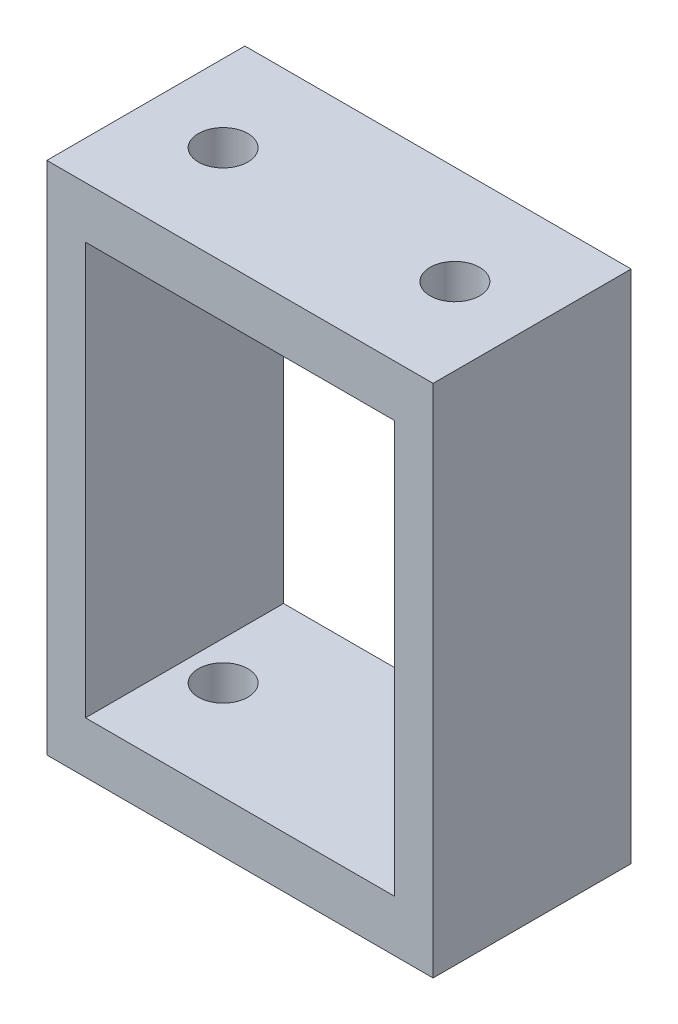
SolidWorks part; units mm, degrees
ref_plane "Front Plane" through (0, 0, 0) normal (0, 0, 1) x (1, 0, 0)
ref_plane "Top Plane" through (0, 0, 0) normal (0, 1, 0) x (1, 0, 0)
ref_plane "Right Plane" through (0, 0, 0) normal (1, 0, 0) x (0, 0, -1)
sketch "Sketch1" plane through (0, 0, 0) normal (0, 0, 1) x (1, 0, 0)
  line L1 (-9.75, -13) -> (9.75, -13)
  line L2 (-9.75, -13) -> (-9.75, 13)
  line L3 (-9.75, 13) -> (9.75, 13)
  line L4 (9.75, -13) -> (9.75, 13)
  line L5 (-9.75, -13) -> (9.75, 13) construction
  line L6 (-9.75, 13) -> (9.75, -13) construction
  line L11 (-6.533, -8.7106) -> (32.8535, 43.8047) construction
  line L12 (-23.2087, 23.2087) -> (23.2087, -23.2087) construction
  point P0 (0, 0)
  point P6 (0, 0)
  dimension "D1" = 19.5
  dimension "D2" = 26
extrude "Boss-Extrude1" add sketch "Sketch1" along normal blind 10
sketch "Sketch2" plane through (0, 0, 10) normal (0, 0, 1) x (1, 0, 0)
  line L1 (-7.8, -10.4) -> (7.8, -10.4)
  line L2 (-7.8, -10.4) -> (-7.8, 10.4)
  line L3 (-7.8, 10.4) -> (7.8, 10.4)
  line L4 (7.8, -10.4) -> (7.8, 10.4)
  line L5 (-7.8, -10.4) -> (7.8, 10.4) construction
  line L6 (-7.8, 10.4) -> (7.8, -10.4) construction
  point P0 (0, 0)
  dimension "D1" = 15.6
  dimension "D2" = 20.8
extrude "Cut-Extrude1" cut sketch "Sketch2" against normal up to next
sketch "Sketch3" plane through (0, -13, 0) normal (0, -1, 0) x (1, 0, 0)
  line L0 (-9.75, 5) -> (-5.85, 5) construction
  line L1 (-9.75, 10) -> (-9.75, 0) construction
  line L2 (9.75, 5) -> (5.85, 5) construction
  line L3 (9.75, 10) -> (9.75, 0) construction
  circle A0 centre (-5.85, 5) radius 1.25
  circle A1 centre (5.85, 5) radius 1.25
  dimension "D3" = 2.5
  dimension "D4" = 2.5
  dimension "D1" = 3.9
  dimension "D2" = 3.9
extrude "Cut-Extrude2" cut sketch "Sketch3" against normal up to next
sketch "Sketch5" plane through (0, 13, 0) normal (0, 1, 0) x (1, 0, 0)
  line L0 (-9.75, -5) -> (-5.85, -5) construction
  line L1 (-9.75, -10) -> (-9.75, 0) construction
  line L2 (9.75, -5) -> (5.85, -5) construction
  line L3 (9.75, -10) -> (9.75, 0) construction
  circle A0 centre (-5.85, -5) radius 1.25
  circle A1 centre (5.85, -5) radius 1.25
  dimension "D3" = 2.5
  dimension "D1" = 3.9
  dimension "D2" = 3.9
extrude "Cut-Extrude3" cut sketch "Sketch5" against normal up to next
equation "\"Mount Width\"= 19.5mm"
equation "\"Mount Inner Size\"= \"Mount Width\" * 0.80"
equation "\"D1@Sketch1\"=\"Mount Width\""
equation "\"D1@Sketch3\"=\"Mount Width\"*0.2"
equation "\"D2@Sketch3\"=\"Mount Width\"*0.2"
equation "\"Hole Dim\"= 2.5mm"
equation "\"D3@Sketch3\"=\"Hole Dim\""
equation "\"D4@Sketch3\"=\"Hole Dim\""
equation "\"D1@Sketch5\"=\"Mount Width\"*0.2"
equation "\"D2@Sketch5\"=\"Mount Width\"*0.2"
equation "\"D3@Sketch5\"=\"Hole Dim\""
equation "\"Mount Height\"= 26mm"
equation "\"D2@Sketch1\"=\"Mount Height\""
equation "\"D1@Sketch2\"=\"Mount Width\" * 0.8"
equation "\"D2@Sketch2\"=\"Mount Height\" * 0.8"
